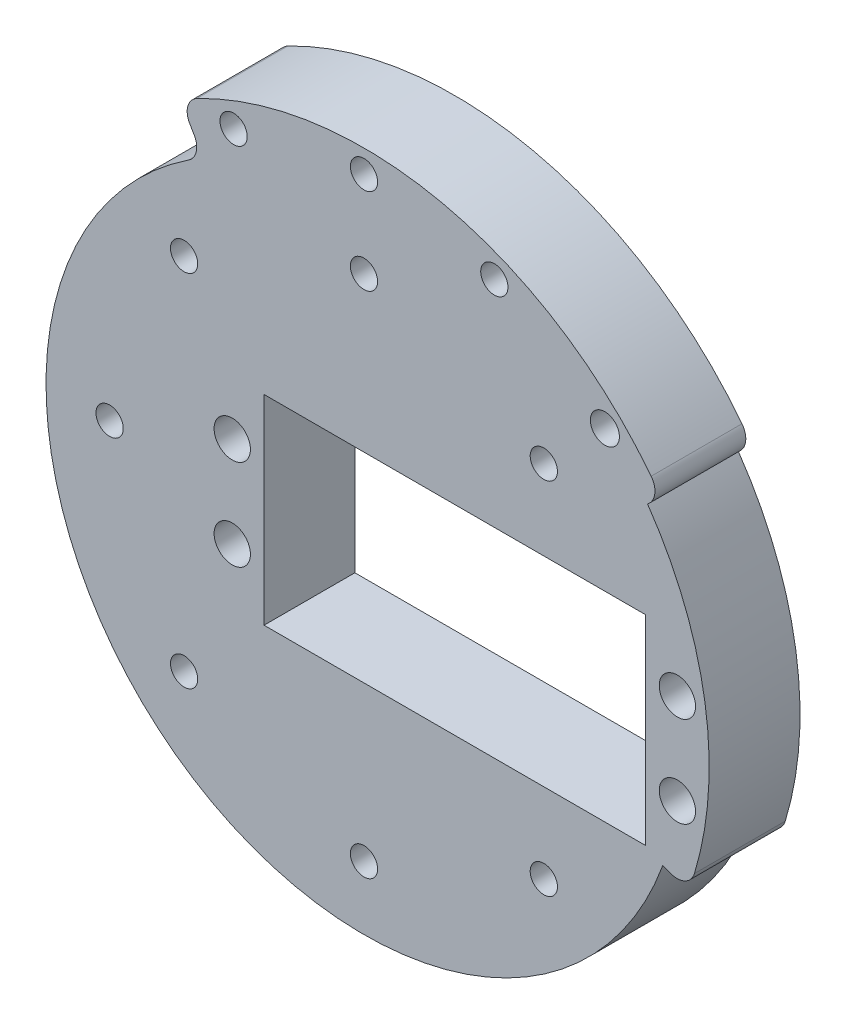
SolidWorks part; units mm, degrees
ref_plane "前视基准面" through (0, 0, 0) normal (0, 0, 1) x (1, 0, 0)
ref_plane "上视基准面" through (0, 0, 0) normal (0, 1, 0) x (1, 0, 0)
ref_plane "右视基准面" through (0, 0, 0) normal (1, 0, 0) x (0, 0, -1)
other "Configuration Table"
sketch "草图2" plane through (0, 0, 0) normal (0, 0, 1) x (1, 0, 0)
  line L0 (-11, 11) -> (-11, -11)
  line L1 (-11, -11) -> (31, -11)
  line L2 (31, -11) -> (31, 11)
  line L3 (31, 11) -> (-11, 11)
  line L4 (0, 0) -> (0, 37.5)
  line L5 (-1000, 0) -> (49000, 0) construction
  line L6 (0, 0) -> (37.2619, 15.4344)
  line L7 (0, 0) -> (26.8701, 26.8701)
  line L8 (0, 0) -> (-14.3506, 34.6455)
  line L9 (0, 0) -> (-21.2362, 36.2357)
  line L10 (0, 0) -> (34.5, 23.9531)
  line L11 (0, 0) -> (39.4687, -14.3603)
  circle A0 centre (0, 0) radius 35
  circle A1 centre (0, 28) radius 1.5
  circle A2 centre (19.799, 19.799) radius 1.5
  circle A3 centre (28, 0) radius 1.5
  circle A4 centre (19.799, -19.799) radius 1.5
  circle A5 centre (0, -28) radius 1.5
  circle A6 centre (-19.799, -19.799) radius 1.5
  circle A7 centre (-28, 0) radius 1.5
  circle A8 centre (-19.799, 19.799) radius 1.5
  circle A9 centre (-14.5, 5) radius 2
  circle A10 centre (-14.5, -5) radius 2
  circle A11 centre (34.5, 5) radius 2
  circle A12 centre (34.5, -5) radius 2
  circle A13 centre (0, 0) radius 38
  circle A16 centre (0, 0) radius 42
  circle A20 centre (0, 0) radius 37.5
  circle A21 centre (26.5165, 26.5165) radius 1.6
  circle A22 centre (0, 0) radius 40
  circle A23 centre (-14.3506, 34.6455) radius 1.5
  circle A24 centre (0, 37.5) radius 1.5
  circle A25 centre (14.3506, 34.6455) radius 1.5
  point P22 (0, 0)
  dimension "D7" = 4
  dimension "D2" = 22.5
  dimension "D3" = 3.2
  dimension "D1" = 8
extrude "凸台-拉伸2" add sketch "草图2" along normal blind 10 contours A0 L5 A7 L0 L3 L9 A8 A9 | L5 A0 L11 L1 L0 A7 A10 A6 A5 A4 | A2 L7 A0 L4 A1 L3 | A1 L4 A0 L8 L3 | L8 A0 L9 L3 | A2 L7 L3 L10 A0 | L6 A0 L10 L3 | L2 L5 A0 A11 L6 L3 | L5 L2 L1 L11 A0 A12 | A25 A20 A24 L4 A0 L7 A21 | A24 A20 A23 L8 A0 L4 | A23 A20 L9 A0 L8 | A25 A13 A21 L10 A22 L9 A23 A24 | A23 A13 L9 A20 | A21 L7 A0 L10 A20 | A25 A20 A21 A13 | A25 A13 A24 A20 | A24 A13 A23 A20 | A21 A20 L10 A13 | A0 L5 A20 L6 A11 | L5 A0 A12 L11 A20 | L5 A20 L11 A13 | A20 L5 A13 L6 | L6 A20 L10 A0 | A20 L6 A13 L10 region at (-21.4101, 12.2088, 0) region at (-4.0519, -18.251, 0) region at (-11.326, 22.7858, 0) region at (-4.9429, 24.472, 0) region at (-16.3686, 32.2233, 0) region at (32.515, -5.3386, 0) region at (9.4162, 22.9548, 0) region at (32.1582, 6.4505, 0) region at (25.5822, 14.2817, 0) region at (20.7805, 17.3068, 0) region at (-7.0243, 35.3136, 0) region at (-17.4579, 33.4553, 0) region at (33.816, -9.5412, 0) region at (31.7678, 17.3462, 0) region at (35.3267, 7.3992, 0) region at (27.9694, 22.8967, 0) region at (13.4703, 32.6485, 0) region at (-19.2348, 33.9314, 0) region at (36.9891, -6.52, 0) region at (33.0697, 18.0571, 0) region at (36.7877, 7.3175, 0) region at (29.4443, 23.5792, 0) region at (-7.3346, 36.8735, 0) region at (7.3346, 36.8735, 0) region at (20.8463, 31.2903, 0)
fillet "圆角1" radius 2 4 edges at (35.7098, -12.9927, 5) (32.8571, 22.8125, 5) (-17.6968, 30.1964, 5) (-20.225, 34.5102, 5)
